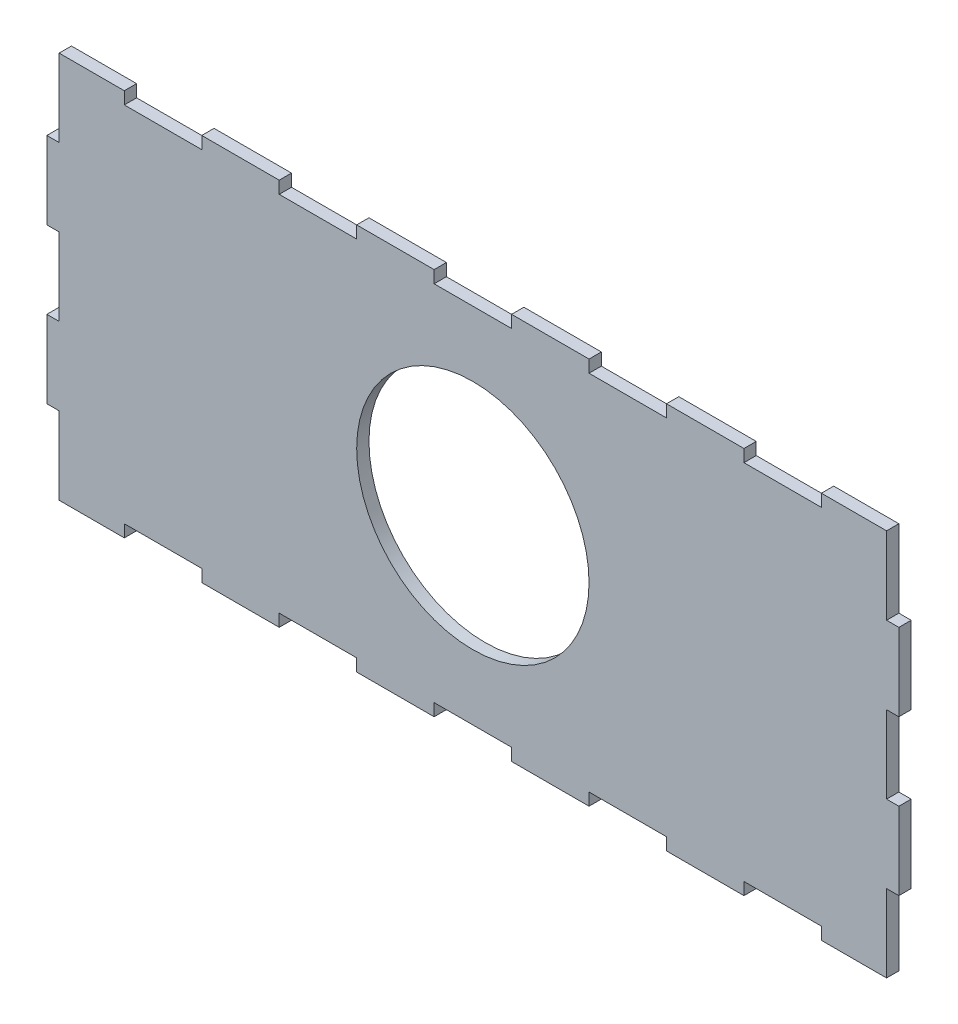
SolidWorks part; units mm, degrees
material "Acrylic (Medium-high impact)"
ref_plane "Front Plane" through (0, 0, 0) normal (0, 0, 1) x (1, 0, 0)
ref_plane "Top Plane" through (0, 0, 0) normal (0, 1, 0) x (1, 0, 0)
ref_plane "Right Plane" through (0, 0, 0) normal (1, 0, 0) x (0, 0, -1)
sketch "Sketch1" plane through (0, 0, 0) normal (0, 0, 1) x (1, 0, 0)
  line L0 (1100, -500) -> (-1100, -500)
  line L1 (1100, -500) -> (1100, 500)
  line L2 (-1100, -500) -> (-1100, 500)
  line L3 (1100, 500) -> (-1100, 500)
  line L4 (1100, -500) -> (-1100, 500) construction
  line L5 (-1100, -500) -> (1100, 500) construction
  point P1 (0, 0)
extrude "Boss-Extrude1" add sketch "Sketch1" along normal blind 750
shell "Shell1" thickness 31.75 removed face at (0, 0, 0) removed face at (0, 500, 375) removed face at (-1100, 0, 375) removed face at (0, -500, 375) removed face at (1100, 0, 375)
scale "Scale1" scale about centroid uniform scaling yes scale factor 0.1
sketch "Sketch36" plane through (0, 0, 735.7125) normal (0, 0, 1) x (1, 0, 0)
  line L0 (-110, -10) -> (-110, 10.0001)
  line L2 (110, -29.9999) -> (106.825, -29.9999)
  line L3 (110, 10.0001) -> (106.825, 10.0001)
  line L4 (110, -49.9999) -> (106.825, -49.9999)
  line L5 (110, -49.9999) -> (110, -29.9999)
  line L7 (106.825, -49.9999) -> (106.825, -29.9999)
  line L8 (110, -9.9999) -> (110, 10.0001)
  line L9 (110, -9.9999) -> (106.825, -9.9999)
  line L10 (106.825, -9.9999) -> (106.825, 10.0001)
  line L12 (110, 50.0001) -> (106.825, 50.0001)
  line L13 (110, 30.0001) -> (110, 50.0001)
  line L14 (110, 30.0001) -> (106.825, 30.0001)
  line L15 (106.825, 30.0001) -> (106.825, 50.0001)
  line L17 (-110, -10) -> (-106.825, -10)
  line L18 (-110, 50) -> (-110, -50) construction
  line L19 (-106.825, -10) -> (-106.825, 10.0001)
  line L20 (-110, 10.0001) -> (-106.825, 10.0001)
  line L21 (-110, -50) -> (-106.825, -50)
  line L22 (-110, -50) -> (-110, -29.9999)
  line L23 (-110, -29.9999) -> (-106.825, -29.9999)
  line L24 (-106.825, -50) -> (-106.825, -29.9999)
  line L25 (-110, 30) -> (-110, 50.0001)
  line L26 (-110, 30) -> (-106.825, 30)
  line L27 (-106.825, 30) -> (-106.825, 50.0001)
  line L28 (-110, 50.0001) -> (-106.825, 50.0001)
  line L29 (50, 50) -> (50, 46.825)
  line L30 (110, 50) -> (-110, 50) construction
  line L31 (50, 50) -> (30, 50)
  line L32 (30, 50) -> (30, 46.825)
  line L33 (90, 50) -> (70, 50)
  line L34 (90, 50) -> (90, 46.825)
  line L35 (90, 46.825) -> (70, 46.825)
  line L36 (70, 50) -> (70, 46.825)
  line L37 (50, 46.825) -> (30, 46.825)
  line L38 (10, 50) -> (10, 46.825)
  line L39 (10, 50) -> (-10, 50)
  line L40 (-10, 50) -> (-10, 46.825)
  line L41 (10, 46.825) -> (-10, 46.825)
  line L42 (-30, 50) -> (-30, 46.825)
  line L43 (-30, 50) -> (-50, 50)
  line L44 (-50, 50) -> (-50, 46.825)
  line L45 (-30, 46.825) -> (-50, 46.825)
  line L46 (-70, 50) -> (-70, 46.825)
  line L47 (-70, 50) -> (-90, 50)
  line L48 (-90, 50) -> (-90, 46.825)
  line L49 (-70, 46.825) -> (-90, 46.825)
  line L50 (50, -50) -> (50, -46.825)
  line L51 (-110, -50) -> (110, -50) construction
  line L52 (50, -50) -> (30, -50)
  line L53 (30, -50) -> (30, -46.825)
  line L54 (90, -50) -> (70, -50)
  line L55 (90, -50) -> (90, -46.825)
  line L56 (90, -46.825) -> (70, -46.825)
  line L57 (70, -50) -> (70, -46.825)
  line L58 (50, -46.825) -> (30, -46.825)
  line L59 (10, -50) -> (10, -46.825)
  line L60 (10, -50) -> (-10, -50)
  line L61 (-10, -50) -> (-10, -46.825)
  line L62 (10, -46.825) -> (-10, -46.825)
  line L63 (-30, -50) -> (-30, -46.825)
  line L64 (-30, -50) -> (-50, -50)
  line L65 (-50, -50) -> (-50, -46.825)
  line L66 (-30, -46.825) -> (-50, -46.825)
  line L67 (-70, -50) -> (-70, -46.825)
  line L68 (-70, -50) -> (-90, -50)
  line L69 (-90, -50) -> (-90, -46.825)
  line L70 (-70, -46.825) -> (-90, -46.825)
  dimension "D1" = 3
  dimension "D2" = 3
  dimension "D3" = 5
  dimension "D4" = 5
extrude "Cut-Extrude18" cut sketch "Sketch36" against normal blind 3.175
sketch "Sketch37" plane through (0, 0, 735.7125) normal (0, 0, 1) x (1, 0, 0)
  circle A0 centre (0, 0) radius 30
extrude "Cut-Extrude19" cut sketch "Sketch37" against normal up to surface (3.175 mm away) up to face at (1.6393, -0.9836, 732.5375)
sketch "Sketch38" plane through (0, 0, 735.7125) normal (0, 0, 1) x (1, 0, 0)
  line L0 (106.825, -49.5954) -> (106.825, -50.2818)
  line L1 (106.825, -29.9999) -> (106.825, -49.9999) construction
  line L2 (106.825, -50.2818) -> (110.1563, -50.2818)
  line L3 (110.1563, -50.2818) -> (110.1563, -49.5954)
  line L4 (110.1563, -49.5954) -> (106.825, -49.5954)
extrude "Cut-Extrude20" cut sketch "Sketch38" against normal up to surface (3.175 mm away) up to face at (30, 0, 732.5375)
